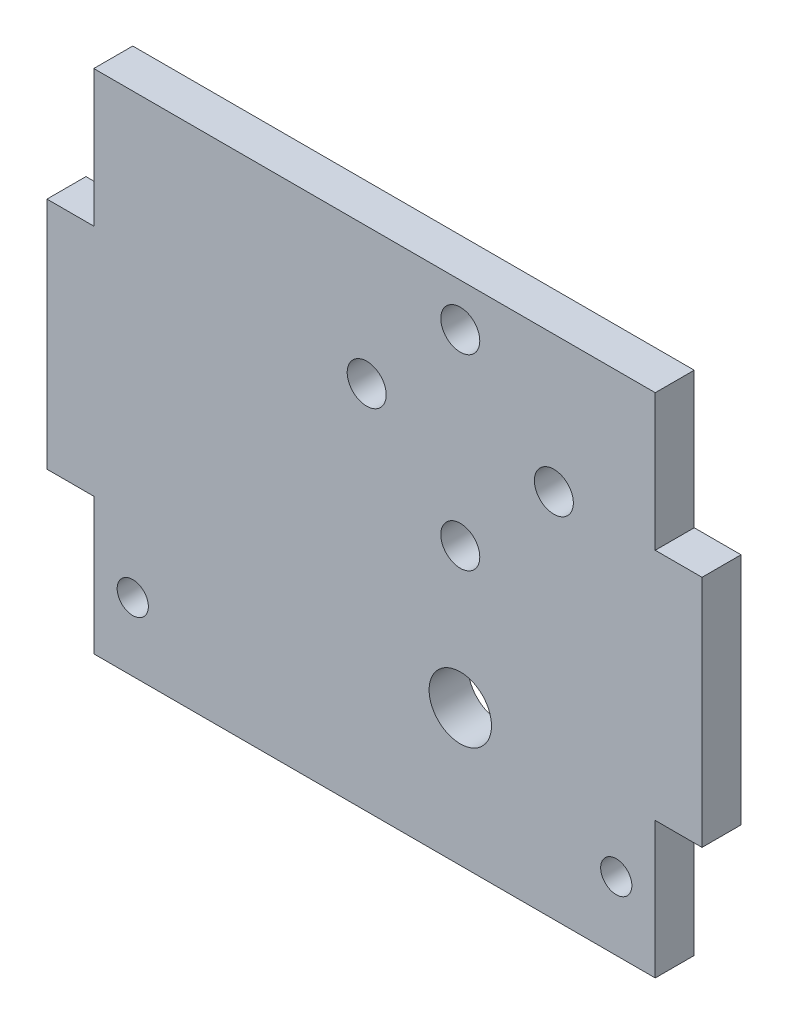
SolidWorks part; units mm, degrees
ref_plane "Front Plane" through (0, 0, 0) normal (0, 0, 1) x (1, 0, 0)
ref_plane "Top Plane" through (0, 0, 0) normal (0, 1, 0) x (1, 0, 0)
ref_plane "Right Plane" through (0, 0, 0) normal (1, 0, 0) x (0, 0, -1)
sketch "Sketch2" plane through (0, 0, 0) normal (0, 0, 1) x (1, 0, 0)
  line L1 (0, 0) -> (50, 0)
  line L2 (0, 0) -> (0, 65)
  line L3 (0, 65) -> (50, 65)
  line L4 (50, 0) -> (50, 65)
  circle A19 centre (25, 59.5) radius 2
  circle A20 centre (13, 47.5) radius 2
  circle A21 centre (37, 47.5) radius 2
  circle A23 centre (25, 17.5) radius 4
extrude "Boss-Extrude1" add sketch "Sketch2" along normal blind 5
sketch "Sketch3" plane through (0, 0, 5) normal (0, 0, 1) x (1, 0, 0)
  line L0 (0, 65) -> (-21, 65)
  line L1 (-21, 65) -> (-21, 0)
  line L2 (-21, 0) -> (0, 0)
  line L3 (0, 65) -> (0, 0)
extrude "Boss-Extrude2" add sketch "Sketch3" against normal up to surface (5 mm away) up to face at (15, 47.5, 0)
sketch "Sketch4" plane through (0, 0, 5) normal (0, 0, 1) x (1, 0, 0)
  line L0 (-21, 65) -> (-22, 65)
  line L1 (-22, 65) -> (-22, 0)
  line L2 (-22, 0) -> (-21, 0)
  line L3 (-21, 0) -> (-21, 65)
extrude "Boss-Extrude3" add sketch "Sketch4" against normal up to surface (5 mm away) up to face at (15, 47.5, 0)
sketch "Sketch5" plane through (0, 0, 5) normal (0, 0, 1) x (1, 0, 0)
  line L0 (-22, 32.5) -> (-22, 47.5)
  line L1 (-22, 65) -> (-22, 0) construction
  line L2 (-22, 32.5) -> (-22, 17.5)
  line L3 (-22, 17.5) -> (-28, 17.5)
  line L4 (-28, 17.5) -> (-28, 47.5)
  line L5 (-28, 47.5) -> (-22, 47.5)
  line L6 (50, 65) -> (-22, 65) construction
  line L7 (14, 65) -> (14, 8.5351)
  line L8 (56, 47.5) -> (50, 47.5)
  line L9 (56, 17.5) -> (56, 47.5)
  line L10 (50, 17.5) -> (56, 17.5)
  line L11 (50, 32.5) -> (50, 17.5)
  line L12 (50, 32.5) -> (50, 47.5)
  line M8 (-22, 65) -> (-22, 0)
  line M10 (50, 0) -> (50, 65)
extrude "Boss-Extrude4" add sketch "Sketch5" against normal up to surface (5 mm away) contours L5 L4 L3 M8 | L10 L9 L8 M10 region at (-25, 32.5, 5) region at (53, 32.5, 5) up to face at (15, 47.5, 0)
sketch "Sketch6" plane through (0, 0, 5) normal (0, 0, 1) x (1, 0, 0)
  circle A1 centre (25, 35.5) radius 2
extrude "Cut-Extrude1" cut sketch "Sketch6" against normal blind 59
sketch "Sketch7" plane through (0, 0, 5) normal (0, 0, 1) x (1, 0, 0)
  line L0 (-22, 47.5) -> (-22, 65)
  line L1 (-22, 56.25) -> (-17, 56.25)
  line L2 (14, 65) -> (14, 56.25)
  line L3 (50, 65) -> (-22, 65) construction
  line L4 (-28, 32.5) -> (-15.3264, 32.5)
  line L5 (-28, 17.5) -> (-28, 47.5) construction
  circle A0 centre (-17, 56.25) radius 1.5
  circle A1 centre (45, 56.25) radius 1.5
  circle A2 centre (45, 8.75) radius 1.5
  circle A3 centre (-17, 8.75) radius 1.5
extrude "Cut-Extrude2" cut sketch "Sketch7" against normal blind 10 contours A0 | A1 region at (-17, 54.7924, 5) region at (45, 56.25, 5)
extrude "Cut-Extrude3" cut sketch "Sketch7<4>" against normal blind 10 contours A2 | A3 region at (45, 8.75, 5)
sketch "Sketch7<4>" plane through (0, 0, 5) normal (0, 0, 1) x (1, 0, 0) same geometry as "Sketch7"
extrude "Boss-Extrude5" add sketch "Sketch7<5>" against normal up to surface (5 mm away) contours A0 | A1 region at (-17, 54.7924, 5) region at (45, 56.25, 5) up to face at (-18.5, 8.75, 0)
sketch "Sketch7<5>" plane through (0, 0, 5) normal (0, 0, 1) x (1, 0, 0) same geometry as "Sketch7"
sketch "Sketch8" plane through (0, 0, 5) normal (0, 0, 1) x (1, 0, 0)
  circle A0 centre (-17, 8.75) radius 2
  circle A1 centre (45, 8.75) radius 2
extrude "Cut-Extrude4" cut sketch "Sketch8" against normal blind 10
sketch "Sketch9" plane through (0, 0, 5) normal (0, 0, 1) x (1, 0, 0)
  circle A0 centre (25, 59.5) radius 2.5
  circle A1 centre (25, 35.5) radius 2.5
  circle A2 centre (13, 47.5) radius 2.5
  circle A3 centre (37, 47.5) radius 2.5
extrude "Cut-Extrude5" cut sketch "Sketch9" against normal blind 10
